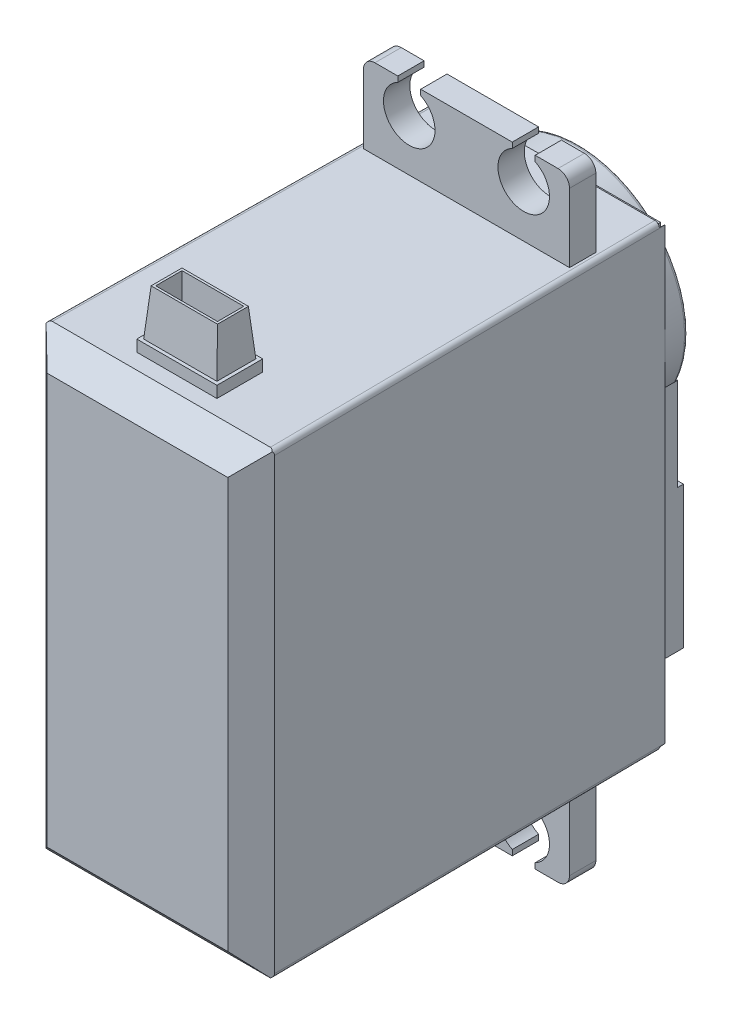
SolidWorks part; units mm, degrees
ref_plane "Alzado" through (0, 0, 0) normal (0, 0, 1) x (1, 0, 0)
ref_plane "Planta" through (0, 0, 0) normal (0, 1, 0) x (1, 0, 0)
ref_plane "Vista lateral" through (0, 0, 0) normal (1, 0, 0) x (0, 0, -1)
sketch "Croquis1" plane through (0, 0, 0) normal (0, 1, 0) x (1, 0, 0)
  line L0 (0, 0) -> (0, 16.262) construction
  line L1 (-9.55, 17.9246) -> (9.55, 17.9246)
  line L2 (-9.55, 17.9246) -> (-9.95, -18.6754)
  line L3 (-9.95, -18.6754) -> (9.95, -18.6754)
  line L4 (9.55, 17.9246) -> (9.95, -18.6754)
  line L5 (-9.55, 17.9246) -> (9.95, -18.6754) construction
  line L6 (-9.95, -18.6754) -> (9.55, 17.9246) construction
  line L7 (0, 0) -> (0, -17.3343) construction
  point P0 (0, 0)
  dimension "D1" = 19.1
  dimension "D2" = 19.9
  dimension "D3" = 9.95
  dimension "D4" = 36.6
extrude "Saliente-Extruir1" add sketch "Croquis1" along normal blind 40
sketch "Croquis2" plane through (0, 0, -17.9246) normal (0, 0, -1) x (-1, 0, 0)
  line L0 (-9.55, 0) -> (-9.55, 40)
  line L1 (-9.55, 40) -> (9.55, 40)
  line L2 (9.55, 40) -> (9.55, 0)
  line L3 (9.55, 0) -> (-9.55, 0)
  line L4 (-9.15, 39.6) -> (9.15, 39.6)
  line L5 (9.15, 39.6) -> (9.15, 0.4)
  line L6 (9.15, 0.4) -> (-9.15, 0.4)
  line L7 (-9.15, 0.4) -> (-9.15, 39.6)
  dimension "D1" = 0.4
  dimension "D2" = 0.4
  dimension "D3" = 0.4
  dimension "D4" = 0.4
extrude "Cortar-Extruir1" cut sketch "Croquis2" against normal blind 0.5
sketch "Croquis3" plane through (0, 0, -17.9246) normal (0, 0, -1) x (-1, 0, 0)
  line L0 (0, 40) -> (0, 20.9) construction
  line L1 (9.55, 40) -> (-9.55, 40) construction
  line L2 (-9.15, 39.6) -> (-9.15, 0.4) construction
  line L3 (-9.55, 40) -> (9.55, 40) construction
  line L4 (-8.65, 26.4028) -> (8.65, 26.4028)
  line L5 (-8.65, 26.4028) -> (-8.65, 5.9)
  line L6 (-8.65, 5.9) -> (8.65, 5.9)
  line L7 (8.65, 26.4028) -> (8.65, 5.9)
  line L8 (-8.65, 28.4) -> (8.65, 5.9) construction
  line L9 (-8.65, 5.9) -> (8.65, 28.4) construction
  line L10 (9.15, 0.4) -> (9.15, 39.6) construction
  line L11 (-9.15, 0.4) -> (9.15, 0.4) construction
  point P11 (0, 17.15)
  dimension "D1" = 19.1
  dimension "D2" = 0.5
  dimension "D3" = 0.5
  dimension "D4" = 5.5
  dimension "D5" = 22.5
extrude "Saliente-Extruir5" add sketch "Croquis3" along normal blind 2
sketch "Croquis4" plane through (0, 0, -17.4246) normal (0, 0, -1) x (-1, 0, 0)
  line L0 (0, 40) -> (0, 20.9) construction
  line L1 (9.55, 40) -> (-9.55, 40) construction
  line L2 (-8.65, 26.4028) -> (8.65, 26.4028)
  arc A0 (8.65, 26.4028) -> (-8.65, 26.4028) centre (0, 30.45) ccw
extrude "Saliente-Extruir10" add sketch "Croquis4" along normal up to surface (2.5 mm away) separate body up to face at (0, 16.1514, -19.9246)
sketch "Croquis5" plane through (0, 0, -17.9246) normal (0, 0, -1) x (-1, 0, 0)
  line L0 (0, 0.4) -> (0, 5.9) construction
  line L1 (-9.15, 0.4) -> (9.15, 0.4) construction
  line L2 (-8.65, 5.9) -> (8.65, 5.9) construction
  line L3 (-4.65, 5.9) -> (-4.65, 0.4) construction
  line L4 (4.65, 5.9) -> (4.65, 0.4) construction
  line L5 (-8.65, 5.9) -> (8.65, 5.9) construction
  line L6 (-4.65, 3.9) -> (4.65, 3.9) construction
  line L7 (-4.65, 5.9) -> (4.65, 5.9)
  arc A0 (-4.65, 5.9) -> (4.65, 5.9) centre (0, 10.3056) ccw
  dimension "D1" = 9.3
  dimension "D2" = 4.65
  dimension "D3" = 2
extrude "Saliente-Extruir11" add sketch "Croquis5" along normal blind 1.7
sketch "Croquis6" plane through (0, 0, -19.9246) normal (0, 0, -1) x (-1, 0, 0)
  line L0 (8.65, 5.9) -> (8.65, 26.4028) construction
  line L1 (-8.65, 5.9) -> (8.65, 5.9)
  line L2 (-8.65, 5.9) -> (-8.65, 18.3)
  line L3 (-8.65, 18.3) -> (-1.8028, 18.3)
  line L4 (8.65, 5.9) -> (8.65, 18.3)
  line L5 (-8.65, 5.9) -> (8.65, 18.3) construction
  line L6 (-8.65, 18.3) -> (8.65, 5.9) construction
  line L7 (-8.65, 20.8) -> (8.65, 20.8) construction
  line L8 (-8.65, 26.4028) -> (-8.65, 5.9) construction
  line L9 (1.8028, 18.3) -> (8.65, 18.3)
  arc A0 (1.8028, 18.3) -> (-1.8028, 18.3) centre (0, 18.9) ccw
  point P4 (0, 12.1)
  dimension "D2" = 3.8
  dimension "D1" = 12.4
  dimension "D3" = 14.9
extrude "Saliente-Extruir12" add sketch "Croquis6" along normal blind 0.5
sketch "Croquis7" plane through (0, 0, -19.9246) normal (0, 0, -1) x (-1, 0, 0)
  circle A0 centre (0, 30.45) radius 6.5
  dimension "D1" = 13
extrude "Saliente-Extruir14" add sketch "Croquis7" along normal blind 1.4 and the other way blind 1.4 separate body
sketch "Croquis8" plane through (0, 0, -21.3246) normal (0, 0, -1) x (-1, 0, 0)
  circle A0 centre (0, 30.45) radius 5.25
  dimension "D1" = 10.5
extrude "Saliente-Extruir15" add sketch "Croquis8" along normal blind 0.6
sketch "Croquis9" plane through (0, 40, 0) normal (0, 1, 0) x (1, 0, 0)
  line L0 (0, 17.4246) -> (0, -18.6754) construction
  line L1 (-9.55, 17.4246) -> (9.55, 17.4246) construction
  line L2 (-9.95, -18.6754) -> (9.95, -18.6754) construction
  line L3 (-9.15, 17.4246) -> (9.15, 17.4246) construction
  line L4 (-9, 12.4246) -> (9, 12.4246)
  line L5 (-9, 12.4246) -> (-9, 10.1246)
  line L6 (-9, 10.1246) -> (9, 10.1246)
  line L7 (9, 12.4246) -> (9, 10.1246)
  line L8 (-9, 12.4246) -> (9, 10.1246) construction
  line L9 (-9, 10.1246) -> (9, 12.4246) construction
  point P6 (0, 11.2746)
  dimension "D1" = 2.3
  dimension "D2" = 5
  dimension "D3" = 18
extrude "Saliente-Extruir16" add sketch "Croquis9" along normal blind 7
sketch "Croquis10" plane through (0, 0, 0) normal (0, -1, 0) x (1, 0, 0)
  line L0 (0, -17.4246) -> (0, 0) construction
  line L1 (9.55, -17.4246) -> (-9.55, -17.4246) construction
  line L3 (-9, -10.1246) -> (9, -10.1246)
  line L4 (-9, -10.1246) -> (-9, -12.4246)
  line L5 (-9, -12.4246) -> (9, -12.4246)
  line L6 (9, -10.1246) -> (9, -12.4246)
  line L7 (-9, -10.1246) -> (9, -12.4246) construction
  line L8 (-9, -12.4246) -> (9, -10.1246) construction
  point P5 (0, -11.2746)
  dimension "D1" = 5
  dimension "D2" = 2.3
  dimension "D3" = 18
extrude "Saliente-Extruir17" add sketch "Croquis10" along normal blind 7
sketch "Croquis11" plane through (0, 0, -12.4246) normal (0, 0, -1) x (-1, 0, 0)
  line L0 (0, 47) -> (0, -7) construction
  line L1 (-9, 47) -> (9, 47) construction
  line L2 (9, -7) -> (-9, -7) construction
  line L3 (-11.8717, 20) -> (13.9364, 20) construction
  line L4 (-9, 40) -> (9, 40) construction
  line L5 (9, 47) -> (9, 40) construction
  line L6 (-9, 47) -> (-9, 40) construction
  line L7 (4, -7.5438) -> (6, -3.6161) construction
  line L8 (4, -3.6161) -> (6, -7.5438) construction
  line L9 (-6, 46.5156) -> (-6, 47.5438)
  line L10 (-6, 47.5438) -> (-4, 47.5438)
  line L11 (-4, 46.5156) -> (-4, 47.5438)
  line L12 (-6, 44.4671) -> (-4, 47.5438) construction
  line L13 (-6, 47.5438) -> (-4, 44.4671) construction
  line L14 (-6, -7.5438) -> (-4, -4.4671) construction
  line L15 (4, 46.5156) -> (4, 47.5438)
  line L16 (4, 47.5438) -> (6, 47.5438)
  line L17 (6, 46.5156) -> (6, 47.5438)
  line L18 (4, 43.6161) -> (6, 47.5438) construction
  line L19 (4, 47.5438) -> (6, 43.6161) construction
  line L20 (-6, -4.4671) -> (-4, -7.5438) construction
  line L21 (-9, 0) -> (9, 0) construction
  line L22 (6, -6.5156) -> (6, -7.5438)
  line L23 (4, -7.5438) -> (6, -7.5438)
  line L24 (4, -6.5156) -> (4, -7.5438)
  line L25 (-4, -6.5156) -> (-4, -7.5438)
  line L26 (-6, -7.5438) -> (-4, -7.5438)
  line L27 (-6, -6.5156) -> (-6, -7.5438)
  arc A0 (4, 46.5156) -> (6, 46.5156) centre (5, 44.5) ccw
  arc A1 (-6, 46.5156) -> (-4, 46.5156) centre (-5, 44.5) ccw
  arc A2 (-6, -6.5156) -> (-4, -6.5156) centre (-5, -4.5) cw
  arc A3 (4, -6.5156) -> (6, -6.5156) centre (5, -4.5) cw
  point P20 (-5, 46.0054)
  point P25 (5, 45.58)
  point P48 (5, -5.58)
  point P49 (-5, -6.0054)
  dimension "D3" = 4.5
  dimension "D4" = 4.5
  dimension "D1" = 4.5
  dimension "D2" = 4.5
  dimension "D5" = 4
  dimension "D6" = 4
  dimension "D7" = 2
  dimension "D8" = 2
extrude "Cortar-Extruir2" cut sketch "Croquis11" against normal through all
sketch "Croquis12" plane through (0, 0, -12.4246) normal (0, 0, -1) x (-1, 0, 0)
  line L0 (0, 47) -> (0, 40) construction
  line L1 (-4, 47) -> (4, 47) construction
  line L2 (-9, 40) -> (9, 40) construction
  line L3 (0, 0) -> (0, -7) construction
  line L4 (4, -7) -> (-4, -7) construction
  line L5 (-9.55, 0) -> (9.55, 0) construction
  line L6 (-0.45, -7) -> (0.45, -7)
  line L7 (-0.45, -7) -> (-0.45, 0)
  line L8 (-0.45, 0) -> (0.45, 0)
  line L9 (0.45, -7) -> (0.45, 0)
  line L10 (-0.45, -7) -> (0.45, 0) construction
  line L11 (-0.45, 0) -> (0.45, -7) construction
  line L13 (-0.45, 40) -> (0.45, 40)
  line L14 (-0.45, 40) -> (-0.45, 47)
  line L15 (-0.45, 47) -> (0.45, 47)
  line L16 (0.45, 40) -> (0.45, 47)
  line L17 (-0.45, 40) -> (0.45, 47) construction
  line L18 (-0.45, 47) -> (0.45, 40) construction
  point P11 (0, -3.5)
  point P18 (0, 43.5)
  dimension "D1" = 0.9
  dimension "D2" = 0.9
extrude "Saliente-Extruir18" add sketch "Croquis12" along normal blind 1
sketch "Croquis13" plane through (-0.45, 0, 0) normal (-1, 0, 0) x (0, 0, 1)
  line L0 (-13.4246, 40) -> (-12.4246, 47)
  line L1 (-12.4246, 47) -> (-13.4246, 47)
  line L2 (-13.4246, 47) -> (-13.4246, 40)
  line L3 (-13.4246, 0) -> (-12.4246, -7)
  line L4 (-13.4246, 0) -> (-13.4246, -7)
  line L5 (-13.4246, -7) -> (-12.4246, -7)
extrude "Cortar-Extruir3" cut sketch "Croquis13" against normal through all
sketch "Croquis14" plane through (0, 0, -20.4246) normal (0, 0, -1) x (-1, 0, 0)
  line L0 (-8.65, 18.3) -> (-8.65, 5.9) construction
  line L1 (-7.65, 6.9) -> (7.65, 6.9)
  line L2 (-7.65, 6.9) -> (-7.65, 17.3)
  line L3 (-7.65, 17.3) -> (7.65, 17.3)
  line L4 (7.65, 6.9) -> (7.65, 17.3)
  line L5 (-7.65, 6.9) -> (7.65, 17.3) construction
  line L6 (-7.65, 17.3) -> (7.65, 6.9) construction
  line L7 (8.65, 5.9) -> (8.65, 26.4028) construction
  line L8 (8.65, 18.3) -> (1.8028, 18.3) construction
  line L9 (-8.65, 5.9) -> (8.65, 5.9) construction
  point P0 (0, 12.1)
  dimension "D1" = 1
  dimension "D2" = 1
  dimension "D3" = 1
  dimension "D4" = 1
extrude "Cortar-Extruir4" cut sketch "Croquis14" against normal blind 0.4
sketch "Croquis15" plane through (0, 0, -21.9246) normal (0, 0, -1) x (-1, 0, 0)
  circle A0 centre (0, 30.45) radius 3
  dimension "D1" = 6
extrude "Cortar-Extruir5" cut sketch "Croquis15" against normal blind 2
sketch "Croquis16" plane through (0, 0, -19.9246) normal (0, 0, -1) x (-1, 0, 0)
  circle A0 centre (0, 30.45) radius 1.1
  dimension "D1" = 2.2
extrude "Cortar-Extruir6" cut sketch "Croquis16" against normal blind 3
sketch "Croquis17" plane through (0, 40, 0) normal (0, 1, 0) x (1, 0, 0)
  line L0 (-9.95, -18.6754) -> (9.95, -18.6754) construction
  line L1 (-3.5, -11.1754) -> (3.5, -11.1754)
  line L2 (-3.5, -11.1754) -> (-3.5, -15.1754)
  line L3 (-3.5, -15.1754) -> (3.5, -15.1754)
  line L4 (3.5, -11.1754) -> (3.5, -15.1754)
  line L5 (-3.5, -11.1754) -> (3.5, -15.1754) construction
  line L6 (-3.5, -15.1754) -> (3.5, -11.1754) construction
  line L7 (0, -18.6754) -> (0, -5.9153) construction
  point P0 (0, -13.1754)
  point P5 (0, -18.6754)
  dimension "D1" = 3.5
  dimension "D2" = 7
  dimension "D3" = 4
extrude "Saliente-Extruir19" add sketch "Croquis17" along normal blind 1
sketch "Croquis18" plane through (0, 41, 0) normal (0, 1, 0) x (1, 0, 0)
  line L0 (-3.5, -11.1754) -> (-3.5, -15.1754) construction
  line L1 (-3.2, -14.8754) -> (3.2, -14.8754)
  line L2 (-3.2, -14.8754) -> (-3.2, -11.4754)
  line L3 (-3.2, -11.4754) -> (3.2, -11.4754)
  line L4 (3.2, -14.8754) -> (3.2, -11.4754)
  line L5 (-3.2, -14.8754) -> (3.2, -11.4754) construction
  line L6 (-3.2, -11.4754) -> (3.2, -14.8754) construction
  line L7 (3.5, -15.1754) -> (3.5, -11.1754) construction
  line L8 (3.5, -11.1754) -> (-3.5, -11.1754) construction
  line L9 (-3.5, -15.1754) -> (3.5, -15.1754) construction
  point P0 (0, -13.1754)
  dimension "D1" = 0.3
  dimension "D2" = 0.3
  dimension "D3" = 0.3
  dimension "D4" = 0.3
extrude "Saliente-Extruir20" add sketch "Croquis18" along normal blind 4
sketch "Croquis20" plane through (0, 0, 14.8754) normal (0, 0, 1) x (1, 0, 0)
  line L0 (0, 41) -> (0, 45) construction
  line L1 (-3.2, 41) -> (3.2, 41) construction
  line L2 (-3.2, 45) -> (3.2, 45) construction
  line L3 (-2.9, 45) -> (2.9, 45)
  line L4 (-2.9, 45) -> (-3.2, 41)
  line L5 (-3.2, 41) -> (-3.2, 45.3007)
  line L6 (-3.2, 45.3007) -> (3.2, 45.3007)
  line L7 (3.2, 45.3007) -> (3.2, 41)
  line L8 (3.2, 41) -> (2.9, 45)
  dimension "D1" = 2.9
  dimension "D2" = 2.9
extrude "Cortar-Extruir7" cut sketch "Croquis20" against normal blind 4
sketch "Croquis22" plane through (3.5, 0, 0) normal (1, 0, 0) x (0, 0, -1)
  line L0 (-14.5254, 45) -> (-11.8254, 45)
  line L1 (-14.8754, 45) -> (-11.4754, 45) construction
  line L2 (-13.1754, 41) -> (-13.1754, 45) construction
  line L3 (-14.8754, 41) -> (-11.4754, 41) construction
  line L4 (-14.5254, 45) -> (-14.8754, 41)
  line L5 (-14.8754, 41) -> (-14.8754, 45.7996)
  line L6 (-14.8754, 45.7996) -> (-11.4754, 45.7996)
  line L7 (-11.4754, 45.7996) -> (-11.4754, 41)
  line L8 (-15.1754, 41) -> (-11.1754, 41) construction
  line L9 (-11.4754, 45) -> (-11.4754, 41) construction
  line L10 (-11.4754, 41) -> (-11.8254, 45)
  dimension "D1" = 2.7
  dimension "D2" = 1.35
extrude "Cortar-Extruir9" cut sketch "Croquis22" against normal through all
sketch "Croquis23" plane through (0, 45, 0) normal (0, 1, 0) x (1, 0, 0)
  line L0 (-2.9, -11.8254) -> (-2.9, -14.5254) construction
  line L1 (-2.7, -14.3254) -> (2.7, -14.3254)
  line L2 (-2.7, -14.3254) -> (-2.7, -12.0254)
  line L3 (-2.7, -12.0254) -> (2.7, -12.0254)
  line L4 (2.7, -14.3254) -> (2.7, -12.0254)
  line L5 (-2.7, -14.3254) -> (2.7, -12.0254) construction
  line L6 (-2.7, -12.0254) -> (2.7, -14.3254) construction
  line L7 (2.9, -14.5254) -> (2.9, -11.8254) construction
  line L8 (-2.9, -14.5254) -> (2.9, -14.5254) construction
  line L9 (-2.9, -11.8254) -> (2.9, -11.8254) construction
  point P0 (0, -13.1754)
  dimension "D1" = 0.2
  dimension "D2" = 0.2
  dimension "D3" = 0.2
  dimension "D4" = 0.2
extrude "Cortar-Extruir10" cut sketch "Croquis23" against normal blind 4
fillet "Redondeo1" radius 1 4 edges at (-9, -7, -11.2746) (9, -7, -11.2746) (9, 47, -11.2746) (-9, 47, -11.2746)
fillet "Redondeo2" radius 0.3 1 edges at (0, 40, -19.9246)
fillet "Redondeo3" radius 0.2 2 edges at (-5.25, 30.45, -21.9246) (-6.5, 30.45, -21.3246)
chamfer "Chaflán1" distance 2 angle 47 4 edges at (9.95, 20, 18.6754) (0, 0, 18.6754) (-9.95, 20, 18.6754) (0, 40, 18.6754)
fillet "Redondeo5" radius 0.4 4 edges at (9.7384, 0, -0.6846) (-9.7391, 0, -0.6246) (-9.7383, 40, -0.697) (9.7383, 40, -0.697)
equation "\"ç\"=0.2"
